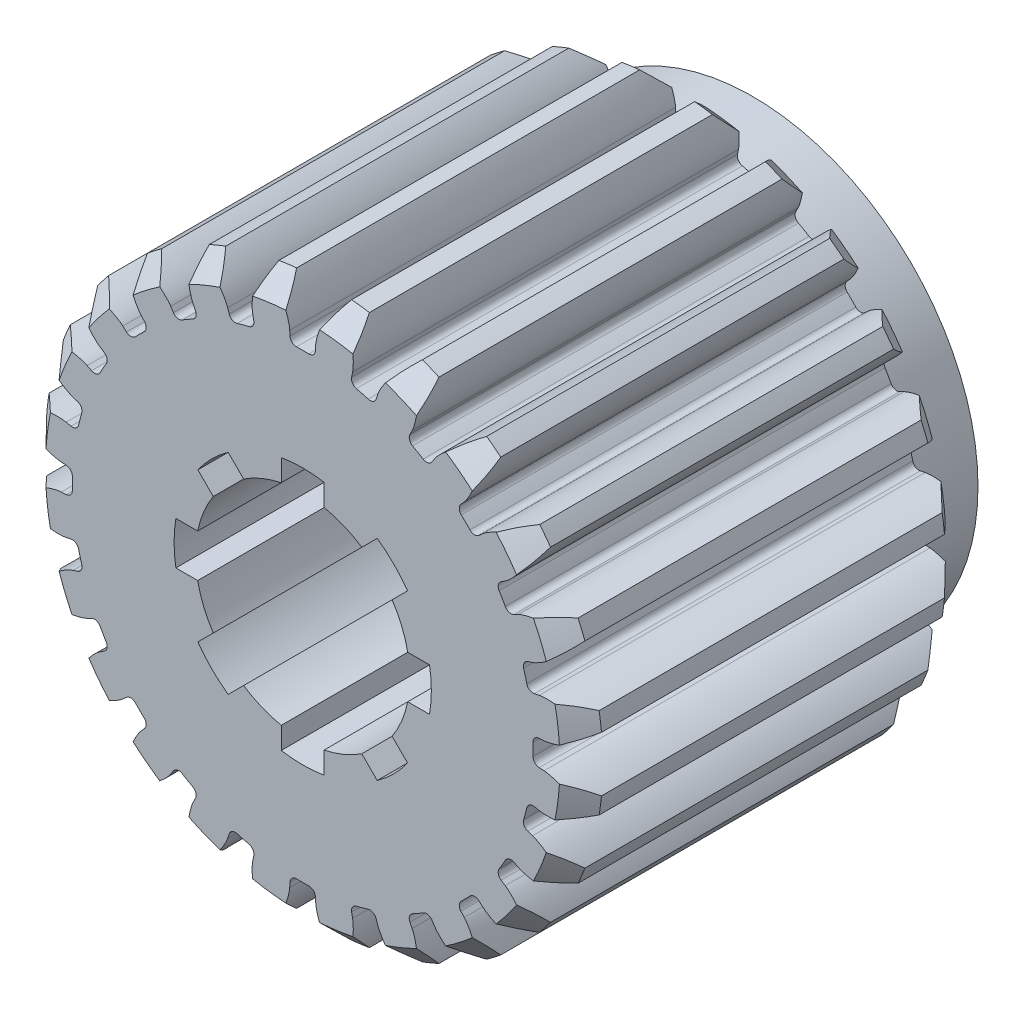
SolidWorks part; units mm, degrees
ref_plane "中间平面" through (0, 0, 0) normal (0, 0, 1) x (1, 0, 0)
ref_plane "上视基准面" through (0, 0, 0) normal (0, 1, 0) x (1, 0, 0)
ref_plane "右视基准面" through (0, 0, 0) normal (1, 0, 0) x (0, 0, -1)
sketch "直齿轮" plane through (0, 0, 0) normal (0, 0, 1) x (1, 0, 0)
  line L0 (0, 0) -> (-0.7848, 11.9743) construction
  line L2 (-0.606, 11.26) -> (0, 0)
  line L3 (0, 0) -> (0, 52) construction
  line L4 (0.7848, 11.9743) -> (0, 0) construction
  line L6 (0, 0) -> (0.606, 11.26)
  circle A0 centre (0, 0) radius 11.2763
  circle A1 centre (0, 0) radius 10.75
  arc A2 (0.7848, 11.9743) -> (-0.7848, 11.9743) centre (0, 0) ccw
  circle A3 centre (0, 0) radius 13
  spline S0 degree 4 poles (-0.5962, 11.2576) (-0.5985, 11.3005) (-0.6071, 11.3858) (-0.6378, 11.5463) (-0.7017, 11.7784) (-0.8433, 12.1697) (-1.1375, 12.7624) (-1.6372, 13.5014) (-2.4761, 14.423) (-3.6097, 15.3442) (-4.9874, 16.1667) (-6.5798, 16.8395) (-8.2422, 17.3101) (-9.9466, 17.5899) (-11.7557, 17.6949) (-13.9974, 17.5907) (-16.6367, 17.1245) (-19.5927, 16.1407) (-22.6677, 14.5536) (-25.4812, 12.5419) (-27.9966, 10.1697) (-29.9143, 7.8309) (-31.3449, 5.6728) (-32.3919, 3.7882) (-33.1415, 2.2348) (-33.8026, 0.6421) (-34.3749, -0.9853) (-34.9793, -3.0537) (-35.4362, -5.1636) (-35.7158, -7.0817) (-35.8543, -8.696) (-35.9033, -9.5504) (-35.9262, -10.1336) (-35.9395, -10.5898) (-35.9461, -11.2367) (-35.9436, -11.7191) (-35.9279, -12.5128) (-35.8987, -13.1226) (-35.8555, -13.8688) (-35.7993, -14.5296) (-35.7297, -15.2433) (-35.6471, -15.9177) (-35.5753, -16.447) (-35.5231, -16.7833) (-35.496, -16.9581) knots 0 0 0 0 0 0.002802 0.005604 0.010661 0.015718 0.02996 0.048734 0.068727 0.096889 0.125051 0.153212 0.181374 0.209535 0.237696 0.271429 0.327752 0.384075 0.440398 0.496721 0.553044 0.609367 0.637529 0.66569 0.693852 0.722013 0.750174 0.778336 0.834659 0.86282 0.876901 0.883942 0.890982 0.900036 0.909091 0.920455 0.931818 0.943182 0.954545 0.965909 0.977273 0.988636 1 1 1 1 1 construction
  spline S1 degree 4 poles (-0.606, 11.26) (-0.6084, 11.3021) (-0.617, 11.3867) (-0.6477, 11.5465) (-0.7114, 11.7777) (-0.8531, 12.1689) (-1.1473, 12.7615) (-1.6469, 13.5003) (-2.4857, 14.4216) (-3.6192, 15.3425) (-4.9967, 16.1647) (-6.5889, 16.8371) (-8.2511, 17.3074) (-9.9551, 17.587) (-11.7639, 17.6918) (-14.0051, 17.5874) (-16.6438, 17.121) (-19.5991, 16.137) (-22.6733, 14.5499) (-25.4861, 12.5383) (-28.0007, 10.1663) (-29.9177, 7.8278) (-31.3477, 5.6699) (-32.3943, 3.7856) (-33.1436, 2.2324) (-33.8044, 0.6399) (-34.3764, -0.9872) (-34.9804, -3.0553) (-35.437, -5.1648) (-35.7163, -7.0825) (-35.8547, -8.6965) (-35.9035, -9.5507) (-35.9263, -10.1339) (-35.9396, -10.59) (-35.9441, -11.0396) (-35.9446, -11.2971) (-35.9441, -11.4262) (-35.9441, -11.4295) knots 0.000048 0.000048 0.000048 0.000048 0.000048 0.002802 0.005604 0.010661 0.015718 0.02996 0.048734 0.068727 0.096889 0.125051 0.153212 0.181374 0.209535 0.237696 0.271429 0.327752 0.384075 0.440398 0.496721 0.553044 0.609367 0.637529 0.66569 0.693852 0.722013 0.750174 0.778336 0.834659 0.86282 0.876901 0.883942 0.890982 0.900036 0.909091 0.909325 0.909325 0.909325 0.909325 0.909325
  spline S2 degree 4 poles (0.5962, 11.2576) (0.5985, 11.3005) (0.6071, 11.3858) (0.6378, 11.5463) (0.7017, 11.7784) (0.8433, 12.1697) (1.1375, 12.7624) (1.6372, 13.5014) (2.4761, 14.423) (3.6097, 15.3442) (4.9874, 16.1667) (6.5798, 16.8395) (8.2422, 17.3101) (9.9466, 17.5899) (11.7557, 17.6949) (13.9974, 17.5907) (16.6367, 17.1245) (19.5927, 16.1407) (22.6677, 14.5536) (25.4812, 12.5419) (27.9966, 10.1697) (29.9143, 7.8309) (31.3449, 5.6728) (32.3919, 3.7882) (33.1415, 2.2348) (33.8026, 0.6421) (34.3749, -0.9853) (34.9793, -3.0537) (35.4362, -5.1636) (35.7158, -7.0817) (35.8543, -8.696) (35.9033, -9.5504) (35.9262, -10.1336) (35.9395, -10.5898) (35.9461, -11.2367) (35.9436, -11.7191) (35.9279, -12.5128) (35.8987, -13.1226) (35.8555, -13.8688) (35.7993, -14.5296) (35.7297, -15.2433) (35.6471, -15.9177) (35.5753, -16.447) (35.5231, -16.7833) (35.496, -16.9581) knots 0 0 0 0 0 0.002802 0.005604 0.010661 0.015718 0.02996 0.048734 0.068727 0.096889 0.125051 0.153212 0.181374 0.209535 0.237696 0.271429 0.327752 0.384075 0.440398 0.496721 0.553044 0.609367 0.637529 0.66569 0.693852 0.722013 0.750174 0.778336 0.834659 0.86282 0.876901 0.883942 0.890982 0.900036 0.909091 0.920455 0.931818 0.943182 0.954545 0.965909 0.977273 0.988636 1 1 1 1 1 construction
  spline S3 degree 4 poles (0.606, 11.26) (0.6084, 11.3021) (0.617, 11.3867) (0.6477, 11.5465) (0.7114, 11.7777) (0.8531, 12.1689) (1.1473, 12.7615) (1.6469, 13.5003) (2.4857, 14.4216) (3.6192, 15.3425) (4.9967, 16.1647) (6.5889, 16.8371) (8.2511, 17.3074) (9.9551, 17.587) (11.7639, 17.6918) (14.0051, 17.5874) (16.6438, 17.121) (19.5991, 16.137) (22.6733, 14.5499) (25.4861, 12.5383) (28.0007, 10.1663) (29.9177, 7.8278) (31.3477, 5.6699) (32.3943, 3.7856) (33.1436, 2.2324) (33.8044, 0.6399) (34.3764, -0.9872) (34.9804, -3.0553) (35.437, -5.1648) (35.7163, -7.0825) (35.8547, -8.6965) (35.9035, -9.5507) (35.9263, -10.1339) (35.9396, -10.59) (35.9441, -11.0396) (35.9446, -11.2971) (35.9441, -11.4262) (35.9441, -11.4295) knots 0.000048 0.000048 0.000048 0.000048 0.000048 0.002802 0.005604 0.010661 0.015718 0.02996 0.048734 0.068727 0.096889 0.125051 0.153212 0.181374 0.209535 0.237696 0.271429 0.327752 0.384075 0.440398 0.496721 0.553044 0.609367 0.637529 0.66569 0.693852 0.722013 0.750174 0.778336 0.834659 0.86282 0.876901 0.883942 0.890982 0.900036 0.909091 0.909325 0.909325 0.909325 0.909325 0.909325
  dimension "基圆直径" = 22.5526
  dimension "齿根圆" = 21.5
  dimension "分度圆" = 24
  dimension "齿顶圆" = 26
  dimension "D1" = 1.5708
sketch "圆" plane through (0, 0, 0) normal (0, 0, 1) x (1, 0, 0)
  circle A0 centre (0, 0) radius 13 construction
  circle A1 centre (0, 0) radius 13
extrude "毛胚" add sketch "圆" along normal mid plane 18
chamfer "轮齿倒角" distance 1 angle 45 2 edges at (13, 0, -9) (13, 0, 9)
sketch "齿形" plane through (0, 0, 0) normal (0, 0, 1) x (1, 0, 0)
  line L4 (0, 0) -> (0.606, 11.26) construction
  line L5 (-0.606, 11.26) -> (0, 0) construction
  line L6 (0, 0) -> (0.606, 11.26)
  line L7 (-0.606, 11.26) -> (0, 0)
  circle A4 centre (0, 0) radius 10.75 construction
  circle A5 centre (0, 0) radius 13 construction
  circle A6 centre (0, 0) radius 10.75
  circle A7 centre (0, 0) radius 13
  spline S1 degree 4 poles (-999.1709, 7.6302) (42.0564, 4.9427) (1.3654, 7.6555) (0.1913, 9.8896) (0.7114, 11.7777) (0.8531, 12.1689) (1.1473, 12.7615) (1.6469, 13.5003) (2.4857, 14.4216) (3.6192, 15.3425) (4.9967, 16.1647) (6.5889, 16.8371) (8.2511, 17.3074) (9.9551, 17.587) (11.7639, 17.6918) (14.0051, 17.5874) (16.6438, 17.121) (19.5991, 16.137) (22.6733, 14.5499) (25.4861, 12.5383) (28.0007, 10.1663) (29.9177, 7.8278) (31.3477, 5.6699) (32.3943, 3.7856) (33.1436, 2.2324) (33.8044, 0.6399) (34.3764, -0.9872) (34.9804, -3.0553) (35.437, -5.1648) (35.7163, -7.0825) (35.8547, -8.6965) (35.9035, -9.5507) (35.9263, -10.1339) (35.9396, -10.59) (35.969, -13.5297) (35.7919, -11.2875) (35.2124, -71.836) (38.4709, 988.417) knots -0.112202 -0.112202 -0.112202 -0.112202 -0.112202 0.002802 0.005604 0.010661 0.015718 0.02996 0.048734 0.068727 0.096889 0.125051 0.153212 0.181374 0.209535 0.237696 0.271429 0.327752 0.384075 0.440398 0.496721 0.553044 0.609367 0.637529 0.66569 0.693852 0.722013 0.750174 0.778336 0.834659 0.86282 0.876901 0.883942 0.890982 0.900036 0.909091 1.049919 1.049919 1.049919 1.049919 1.049919 only from (0.606, 11.26) to (35.9441, -11.4295) construction
  spline S3 degree 4 poles (999.1709, 7.6302) (-42.0564, 4.9427) (-1.3654, 7.6555) (-0.1913, 9.8896) (-0.7114, 11.7777) (-0.8531, 12.1689) (-1.1473, 12.7615) (-1.6469, 13.5003) (-2.4857, 14.4216) (-3.6192, 15.3425) (-4.9967, 16.1647) (-6.5889, 16.8371) (-8.2511, 17.3074) (-9.9551, 17.587) (-11.7639, 17.6918) (-14.0051, 17.5874) (-16.6438, 17.121) (-19.5991, 16.137) (-22.6733, 14.5499) (-25.4861, 12.5383) (-28.0007, 10.1663) (-29.9177, 7.8278) (-31.3477, 5.6699) (-32.3943, 3.7856) (-33.1436, 2.2324) (-33.8044, 0.6399) (-34.3764, -0.9872) (-34.9804, -3.0553) (-35.437, -5.1648) (-35.7163, -7.0825) (-35.8547, -8.6965) (-35.9035, -9.5507) (-35.9263, -10.1339) (-35.9396, -10.59) (-35.969, -13.5297) (-35.7919, -11.2875) (-35.2124, -71.836) (-38.4707, 988.4173) knots -0.112202 -0.112202 -0.112202 -0.112202 -0.112202 0.002802 0.005604 0.010661 0.015718 0.02996 0.048734 0.068727 0.096889 0.125051 0.153212 0.181374 0.209535 0.237696 0.271429 0.327752 0.384075 0.440398 0.496721 0.553044 0.609367 0.637529 0.66569 0.693852 0.722013 0.750174 0.778336 0.834659 0.86282 0.876901 0.883942 0.890982 0.900036 0.909091 1.049919 1.049919 1.049919 1.049919 1.049919 only from (-0.606, 11.26) to (-35.9441, -11.4295) construction
  spline S4 degree 4 poles (0.606, 11.26) (0.6084, 11.3021) (0.617, 11.3867) (0.6477, 11.5465) (0.7114, 11.7777) (0.8531, 12.1689) (1.1473, 12.7615) (1.6469, 13.5003) (2.4857, 14.4216) (3.6192, 15.3425) (4.9967, 16.1647) (6.5889, 16.8371) (8.2511, 17.3074) (9.9551, 17.587) (11.7639, 17.6918) (14.0051, 17.5874) (16.6438, 17.121) (19.5991, 16.137) (22.6733, 14.5499) (25.4861, 12.5383) (28.0007, 10.1663) (29.9177, 7.8278) (31.3477, 5.6699) (32.3943, 3.7856) (33.1436, 2.2324) (33.8044, 0.6399) (34.3764, -0.9872) (34.9804, -3.0553) (35.437, -5.1648) (35.7163, -7.0825) (35.8547, -8.6965) (35.9035, -9.5507) (35.9263, -10.1339) (35.9396, -10.59) (35.9441, -11.0396) (35.9446, -11.2971) (35.9441, -11.4262) (35.9441, -11.4295) knots 0.000048 0.000048 0.000048 0.000048 0.000048 0.002802 0.005604 0.010661 0.015718 0.02996 0.048734 0.068727 0.096889 0.125051 0.153212 0.181374 0.209535 0.237696 0.271429 0.327752 0.384075 0.440398 0.496721 0.553044 0.609367 0.637529 0.66569 0.693852 0.722013 0.750174 0.778336 0.834659 0.86282 0.876901 0.883942 0.890982 0.900036 0.909091 0.909325 0.909325 0.909325 0.909325 0.909325
  spline S5 degree 4 poles (-0.606, 11.26) (-0.6084, 11.3021) (-0.617, 11.3867) (-0.6477, 11.5465) (-0.7114, 11.7777) (-0.8531, 12.1689) (-1.1473, 12.7615) (-1.6469, 13.5003) (-2.4857, 14.4216) (-3.6192, 15.3425) (-4.9967, 16.1647) (-6.5889, 16.8371) (-8.2511, 17.3074) (-9.9551, 17.587) (-11.7639, 17.6918) (-14.0051, 17.5874) (-16.6438, 17.121) (-19.5991, 16.137) (-22.6733, 14.5499) (-25.4861, 12.5383) (-28.0007, 10.1663) (-29.9177, 7.8278) (-31.3477, 5.6699) (-32.3943, 3.7856) (-33.1436, 2.2324) (-33.8044, 0.6399) (-34.3764, -0.9872) (-34.9804, -3.0553) (-35.437, -5.1648) (-35.7163, -7.0825) (-35.8547, -8.6965) (-35.9035, -9.5507) (-35.9263, -10.1339) (-35.9396, -10.59) (-35.9441, -11.0396) (-35.9446, -11.2971) (-35.9441, -11.4262) (-35.9441, -11.4295) knots 0.000048 0.000048 0.000048 0.000048 0.000048 0.002802 0.005604 0.010661 0.015718 0.02996 0.048734 0.068727 0.096889 0.125051 0.153212 0.181374 0.209535 0.237696 0.271429 0.327752 0.384075 0.440398 0.496721 0.553044 0.609367 0.637529 0.66569 0.693852 0.722013 0.750174 0.778336 0.834659 0.86282 0.876901 0.883942 0.890982 0.900036 0.909091 0.909325 0.909325 0.909325 0.909325 0.909325
extrude "插齿" cut sketch "齿形" against normal mid plane 18 contours S5 A6 S4 A7 region at (0, 12.0295, 0)
fillet "圆角1" [suppressed] radius 0.3
pattern_circular "圆周阵列1" [suppressed] count 24 over 360 of bodies 165
fillet "圆角2" radius 0.3 2 edges at (0.5778, 10.7345, 0) (-0.5778, 10.7345, 0)
pattern_circular "圆周阵列2" count 24 over 360 about axis through (0, 0, 9) along (0, 0, -1) of "圆角2", "插齿"
sketch "分度圆" plane through (0, 0, 0) normal (0, 0, 1) x (1, 0, 0)
  circle A0 centre (0, 0) radius 12 construction
  circle A1 centre (0, 0) radius 12 construction
sketch "草图1" plane through (0, 0, 9) normal (0, 0, 1) x (1, 0, 0)
  circle A0 centre (0, 0) radius 10.5
  dimension "D1" = 21
extrude "凸台-拉伸1" add sketch "草图1" against normal blind 21
sketch "草图2" plane through (0, 0, 9) normal (0, 0, 1) x (1, 0, 0)
  circle A0 centre (0, 0) radius 5
  dimension "D1" = 10
extrude "切除-拉伸1" cut sketch "草图2" against normal through all
sketch "草图3" plane through (0, 0, 9) normal (0, 0, 1) x (1, 0, 0)
  line L0 (0, 0) -> (0, 6) construction
  line L1 (1, -5.9161) -> (1, 5.9161)
  line L2 (-1, -5.9161) -> (-1, 5.9161)
  line L3 (-1, 0) -> (-1, 6) construction
  line L4 (1, 0) -> (1, 6) construction
  arc A0 (-1, -5.9161) -> (1, -5.9161) centre (0, 0) ccw
  arc A1 (1, 5.9161) -> (-1, 5.9161) centre (0, 0) ccw
  dimension "D2" = 1
  dimension "D1" = 6
  dimension "D3" = 1
extrude "切除-拉伸2" cut sketch "草图3" against normal through all
pattern_circular "阵列(圆周)1" count 8 over 360 about axis through (0, 0, 9) along (0, 0, 1) of "切除-拉伸2"
equation "\"m\" = 1'模数"
equation "\"z\" = 24'齿数"
equation "\"a\"= 20'压力角（常见为20°）"
equation "\"B\" = 18'齿宽"
equation "\"C1\"= 1'轮齿倒角（若设为0，则无倒角）"
equation "\"x\"= 0'变位系数（不懂勿动）"
equation "\"ha\"= 1'齿顶高系数（不懂勿动）"
equation "\"c\"= 0.25'顶隙系数（不懂勿动）"
equation "\"基圆直径@直齿轮\"= \"m\" * \"z\" * cos ( \"a\" )"
equation "\"齿根圆@直齿轮\" = \"m\" * ( \"z\" - 2 * ( \"ha\" - \"x\" + \"c\" ) )"
equation "\"分度圆@直齿轮\"=\"m\" * \"z\""
equation "\"齿顶圆@直齿轮\" = \"m\" * ( \"z\" + 2 * ( \"ha\" + \"x\" ) )"
equation "\"R\"= 0.3'齿根圆角"
equation "\"D1\"= \"R\""
equation "\"D1@毛胚\" = \"B\""
equation "\"D1@轮齿倒角\" = IIF ( \"C1\" > 0 , \"C1\" , 0.001 )"
equation "\"轮齿倒角\"= IIF ( \"C1\" > 0 , \"unsuppressed\" , \"suppressed\" )"
equation "\"D1@插齿\" = \"B\""
equation "\"D1@圆周阵列1\" = \"z\""
equation "\"D1@直齿轮\"= \"m\" * ( pi / 2 ) - 2 * \"m\" * tan ( \"a\" ) * \"x\"'作者：机械菌-"
equation "\"D1@圆角1\"=\"R\""
equation "\"圆角1\" = IIF ( \"m\" * ( \"z\" - 2 * ( \"ha\" - \"x\" + \"c\" ) ) > \"m\" * \"z\" * cos ( \"a\" ) , \"unsuppressed\" , \"suppressed\" )"
equation "\"圆周阵列1\"= IIF ( \"m\" * ( \"z\" - 2 * ( \"ha\" - \"x\" + \"c\" ) ) > \"m\" * \"z\" * cos ( \"a\" ) , \"unsuppressed\" , \"suppressed\" )"
equation "\"D1@圆角2\"=\"R\""
equation "\"D1@圆周阵列2\" = \"z\""
equation "\"圆角2\" = IIF ( \"m\" * ( \"z\" - 2 * ( \"ha\" - \"x\" + \"c\" ) ) < \"m\" * \"z\" * cos ( \"a\" ) , \"unsuppressed\" , \"suppressed\" )"
equation "\"圆周阵列2\"= IIF ( \"m\" *  ( \"z\" - 2 *  ( \"ha\" - \"x\" + \"c\" )  )  < \"m\" * \"z\" * cos ( \"a\" )  ,  unsuppressed  ,  suppressed  ) "
